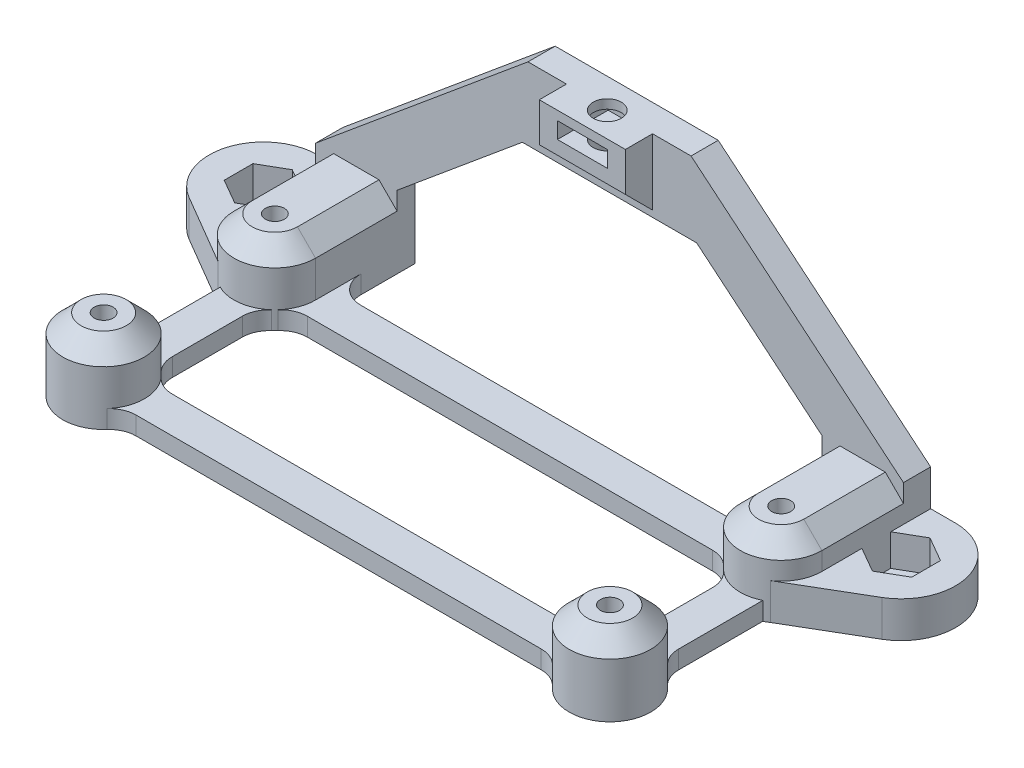
SolidWorks part; units mm, degrees
ref_plane "Front Plane" through (0, 0, 0) normal (0, 0, 1) x (1, 0, 0)
ref_plane "Top Plane" through (0, 0, 0) normal (0, 1, 0) x (1, 0, 0)
ref_plane "Right Plane" through (0, 0, 0) normal (1, 0, 0) x (0, 0, -1)
sketch "Sketch1" plane through (0, 0, 0) normal (0, 1, 0) x (1, 0, 0)
  line L0 (0, 0) -> (-49.6209, 0) construction
  line L1 (-32.45, -37.5) -> (-32.45, -25.5)
  line L2 (-27.95, -37.5) -> (27.95, -37.5) construction
  line L3 (-27.95, -37.5) -> (-27.95, -56.4) construction
  line L4 (-27.95, -56.4) -> (27.95, -56.4) construction
  line L5 (27.95, -37.5) -> (27.95, -56.4) construction
  line L6 (-32.45, -25.5) -> (-23.45, -25.5)
  line L7 (-23.45, -25.5) -> (-23.45, -37.5)
  line L8 (0, -37.5) -> (0, -56.4) construction
  line L9 (32.45, -37.5) -> (32.45, -25.5)
  line L10 (23.45, -25.5) -> (23.45, -37.5)
  line L11 (32.45, -25.5) -> (23.45, -25.5)
  circle A2 centre (27.95, -56.4) radius 4.5
  circle A3 centre (-27.95, -56.4) radius 4.5
  circle A4 centre (-27.95, -37.5) radius 1.05
  circle A5 centre (27.95, -37.5) radius 1.05
  circle A6 centre (-27.95, -56.4) radius 1.05
  circle A7 centre (27.95, -56.4) radius 1.05
  arc A8 (-32.45, -37.5) -> (-23.45, -37.5) centre (-27.95, -37.5) ccw
  arc A9 (32.45, -37.5) -> (23.45, -37.5) centre (27.95, -37.5) cw
  point P7 (0, -37.5)
  dimension "D1" = 9
  dimension "D2" = 2.1
  dimension "D4" = 12
  dimension "D3" = 18.9
  dimension "D5" = 25.5
  dimension "D6" = 55.9
extrude "Boss-Extrude1" add sketch "Sketch1" along normal blind 8
sketch "Sketch2" plane through (32.45, 0, 0) normal (1, 0, 0) x (0, 0, -1)
  line L0 (-25.5, 0) -> (-25.5, 27.5)
  line L2 (0, 27.5) -> (0, 0) construction
  line L3 (-25.5, 0) -> (-28.5, 0)
  line L4 (-28.5, 0) -> (-28.5, 27.5)
  line L7 (-28.5, 27.5) -> (-25.5, 27.5)
  line L8 (0, 27.5) -> (-25.5, 27.5) construction
  dimension "D1" = 3
  dimension "D2" = 27.5
extrude "Boss-Extrude2" add sketch "Sketch2" against normal up to surface (64.9 mm away) up to face at (-32.45, 4, 31.5)
sketch "Sketch3" plane through (0, 0, 28.5) normal (0, 0, 1) x (1, 0, 0)
  line L0 (-32.45, 8) -> (-9, 27.5)
  line L1 (-9, 27.5) -> (9, 27.5) construction
  line L3 (-32.45, 27.5) -> (32.45, 27.5) construction
  line L4 (-32.45, 27.5) -> (-9, 27.5)
  line L6 (9, 27.5) -> (32.45, 8)
  line L7 (32.45, 8) -> (32.45, 27.5)
  line L10 (-32.45, 27.5) -> (-32.45, 8)
  line L11 (-23.45, 8) -> (-23.45, 0)
  line L12 (-23.45, 0) -> (23.45, 0)
  line L13 (23.45, 0) -> (23.45, 8)
  line L14 (23.45, 8) -> (9.6205, 19.5)
  line L15 (9.6205, 19.5) -> (-9.6205, 19.5)
  line L16 (-9.6205, 19.5) -> (-23.45, 8)
  line L17 (32.45, 27.5) -> (9, 27.5)
  point P9 (0, 27.5)
  point P24 (0, 19.5)
  dimension "D1" = 18
  dimension "D2" = 8
extrude "Cut-Extrude1" cut sketch "Sketch3" against normal through all
sketch "Sketch4" plane through (0, 0, 0) normal (0, -1, 0) x (1, 0, 0)
  line L0 (-27.95, 37.5) -> (27.95, 37.5) construction
  line L1 (27.95, 37.5) -> (27.95, 56.4) construction
  line L2 (-27.95, 56.4) -> (27.95, 56.4) construction
  line L3 (-27.95, 37.5) -> (-27.95, 56.4) construction
  line L4 (-27.95, 37.5) -> (27.95, 37.5) construction
  line L5 (27.95, 37.5) -> (27.95, 56.4) construction
  line L6 (-27.95, 56.4) -> (27.95, 56.4) construction
  line L7 (-27.95, 37.5) -> (-27.95, 56.4) construction
  line L8 (-29.95, 58.4) -> (29.95, 58.4)
  line L9 (29.95, 35.5) -> (29.95, 58.4)
  line L10 (-29.95, 35.5) -> (29.95, 35.5)
  line L11 (-29.95, 35.5) -> (-29.95, 58.4)
  line L12 (-25.95, 54.4) -> (25.95, 54.4)
  line L13 (25.95, 39.5) -> (25.95, 54.4)
  line L14 (-25.95, 39.5) -> (25.95, 39.5)
  line L15 (-25.95, 39.5) -> (-25.95, 54.4)
  dimension "D1" = 2
  dimension "D2" = 2
extrude "Boss-Extrude3" add sketch "Sketch4" against normal blind 2
sketch "Sketch7" plane through (0, 27.5, 0) normal (0, 1, 0) x (1, 0, 0)
  line L0 (-9, -25.5) -> (9, -25.5) construction
  line L1 (-2.75, -26) -> (2.75, -26) construction
  line L2 (-2.75, -26) -> (-2.75, -31.5) construction
  line L3 (-2.75, -31.5) -> (2.75, -31.5) construction
  line L4 (2.75, -26) -> (2.75, -31.5) construction
  line L5 (-9, -28.5) -> (9, -28.5) construction
  line L6 (-4.75, -28.5) -> (4.75, -28.5)
  line L7 (-4.75, -28.5) -> (-4.75, -31.5)
  line L8 (-4.75, -31.5) -> (4.75, -31.5)
  line L9 (4.75, -28.5) -> (4.75, -31.5)
  point P4 (0, -26)
  point P14 (0, -28.5)
  dimension "D1" = 5.5
  dimension "D2" = 0.5
  dimension "D3" = 2
extrude "Boss-Extrude5" add sketch "Sketch7" against normal blind 4.3
sketch "Sketch8" plane through (0, 27.5, 0) normal (0, 1, 0) x (1, 0, 0)
  line L1 (-2.75, -26) -> (2.75, -26)
  line L2 (-2.75, -26) -> (-2.75, -31.5)
  line L3 (-2.75, -31.5) -> (2.75, -31.5)
  line L4 (2.75, -26) -> (2.75, -31.5)
extrude "Cut-Extrude3" cut sketch "Sketch8" against normal blind 1.8 from offset 1 offset against normal yes
chamfer "Chamfer3" distance 3 angle 45 1 edges at (0, 23.2, 28.5)
sketch "Sketch9" plane through (0, 27.5, 0) normal (0, 1, 0) x (1, 0, 0)
  line L0 (-2.75, -26) -> (-2.75, -31.5) construction
  line L1 (-2.75, -26) -> (2.75, -26) construction
  circle A0 centre (0, -28.75) radius 1.55
  point P5 (-2.75, -28.75)
  point P8 (0, -26)
  dimension "D1" = 3.1
extrude "Cut-Extrude4" cut sketch "Sketch9" against normal blind 5.4
sketch "Sketch10" plane through (0, 0, 0) normal (0, -1, 0) x (1, 0, 0)
  line L0 (-32.45, 25.5) -> (-35.2, 25.5)
  line L1 (-35.2, 28.3246) -> (-32.45, 29.9123)
  line L2 (-32.45, 29.9123) -> (-32.45, 33.0877)
  line L3 (-32.45, 33.0877) -> (-35.2, 34.6754)
  line L4 (-35.2, 34.6754) -> (-37.95, 33.0877)
  line L5 (-37.95, 33.0877) -> (-37.95, 29.9123)
  line L6 (-37.95, 29.9123) -> (-35.2, 28.3246)
  line L7 (-32.45, 25.5) -> (-32.45, 37.5) construction
  line L8 (-29.95, 41.5311) -> (-38.2337, 36.6766)
  line L10 (-29.95, 41.5311) -> (-29.95, 25.5)
  line L11 (-23.45, 25.5) -> (-32.45, 25.5) construction
  line L12 (-29.95, 25.5) -> (-32.45, 25.5)
  circle A0 centre (-35.2, 31.5) radius 2.75 construction
  arc A2 (-35.2, 25.5) -> (-38.2337, 36.6766) centre (-35.2, 31.5) cw
  dimension "D2" = 6
  dimension "D1" = 5.5
extrude "Boss-Extrude6" add sketch "Sketch10" against normal blind 4
sketch "Sketch11" plane through (0, 0, 0) normal (0, -1, 0) x (1, 0, 0)
  line L1 (-37.95, 33.0877) -> (-37.95, 29.9123) construction
  line L2 (-37.95, 29.9123) -> (-35.2, 28.3246) construction
  line L3 (-35.2, 28.3246) -> (-32.45, 29.9123) construction
  line L4 (-32.45, 29.9123) -> (-32.45, 33.0877) construction
  line L5 (-32.45, 33.0877) -> (-35.2, 34.6754) construction
  line L6 (-35.2, 34.6754) -> (-37.95, 33.0877) construction
  line L7 (-37.95, 33.0877) -> (-37.95, 29.9123)
  line L8 (-37.95, 29.9123) -> (-35.2, 28.3246)
  line L9 (-35.2, 28.3246) -> (-32.45, 29.9123)
  line L10 (-32.45, 29.9123) -> (-32.45, 33.0877)
  line L11 (-32.45, 33.0877) -> (-35.2, 34.6754)
  line L12 (-35.2, 34.6754) -> (-37.95, 33.0877)
  circle A1 centre (-35.2, 31.5) radius 1.5
  dimension "D1" = 3
extrude "Boss-Extrude7" add sketch "Sketch11" against normal blind 0.5
mirror "Mirror1" about plane through (0, 0, 0) normal (1, 0, 0) of "Boss-Extrude7", "Boss-Extrude6"
fillet "Fillet2" radius 3 14 edges at (-23.45, 1, 35.5) (23.45, 1, 35.5) (-29.95, 1, 52.3689) (29.95, 1, 52.3689) (23.9189, 1, 58.4) (-23.9189, 1, 58.4) (25.95, 1, 52.3689) (23.9189, 1, 54.4) (25.95, 1, 41.5311) (23.9189, 1, 39.5) (-25.95, 1, 52.3689) (-23.9189, 1, 54.4) (-23.9189, 1, 39.5) (-25.95, 1, 41.5311)
chamfer "Chamfer4" distance 1 angle 45 2 edges at (23.45, 4, 25.5) (-23.45, 4, 25.5)
chamfer "Chamfer5" distance 2 angle 45 8 edges at (27.95, 8, 60.9) (23.45, 8, 33) (32.45, 8, 33) (27.95, 8, 42) (-32.45, 8, 33) (-23.45, 8, 33) (-27.95, 8, 42) (-27.95, 8, 60.9)
sketch "Sketch12" plane through (0, 0, 26) normal (0, 0, 1) x (1, 0, 0)
  line L1 (-2.75, 26.5) -> (2.75, 26.5)
  line L2 (-2.75, 26.5) -> (-2.75, 24.7)
  line L3 (-2.75, 24.7) -> (2.75, 24.7)
  line L4 (2.75, 26.5) -> (2.75, 24.7)
extrude "Cut-Extrude5" cut sketch "Sketch12" against normal blind 0.1
